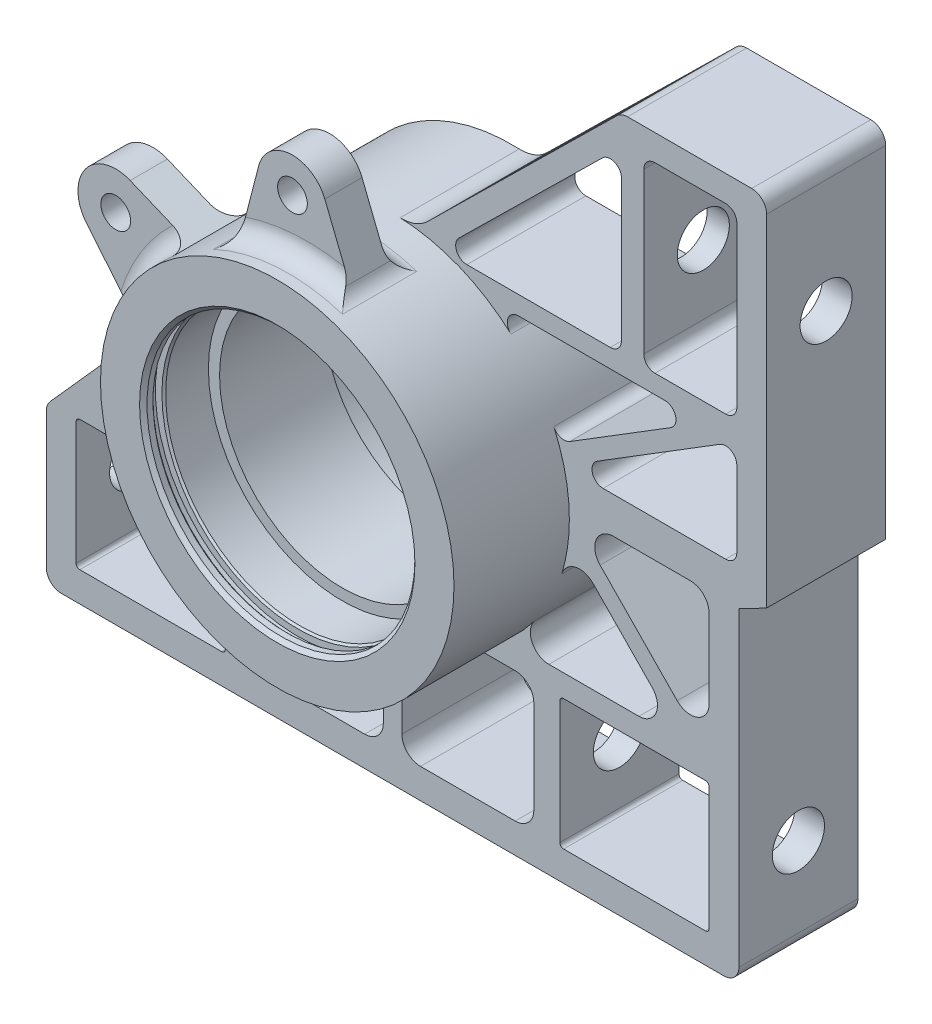
SolidWorks part; units mm, degrees
material "7075-T6 (SN)"
ref_plane "Front Plane" through (0, 0, 0) normal (0, 0, 1) x (1, 0, 0)
ref_plane "Top Plane" through (0, 0, 0) normal (0, 1, 0) x (1, 0, 0)
ref_plane "Right Plane" through (0, 0, 0) normal (1, 0, 0) x (0, 0, -1)
sketch "Sketch1" plane through (0, 0, 0) normal (0, 0, 1) x (1, 0, 0)
  circle A0 centre (0, 0) radius 36
  circle A1 centre (0, 0) radius 47.5
  dimension "D1" = 72
  dimension "D2" = 95
extrude "Boss-Extrude1" add sketch "Sketch1" along normal blind 60 and the other way blind 3
sketch "Sketch2" plane through (0, 0, -3) normal (0, 0, -1) x (-1, 0, 0)
  line L0 (0, 0) -> (0, -85.5) construction
  line L1 (-89.05, -85.5) -> (89.05, -85.5)
  line L2 (93.05, -81.5) -> (93.05, -45.0252)
  line L4 (-63.1377, 101.5) -> (-96.5, 101.5)
  line L6 (-65, -60) -> (65, -60) construction
  line L7 (-65, -60) -> (-65, 70) construction
  line L8 (-65, 70) -> (-80, 70) construction
  line L9 (-84.05, -77.5) -> (-45.95, -77.5)
  line L10 (-85.05, -76.5) -> (-85.05, -43.5)
  line L11 (-84.05, -42.5) -> (-45.95, -42.5)
  line L12 (-44.95, -76.5) -> (-44.95, -43.5)
  line L13 (-85.05, -77.5) -> (-44.95, -42.5) construction
  line L14 (-85.05, -42.5) -> (-44.95, -77.5) construction
  line L15 (45.95, -77.5) -> (84.05, -77.5)
  line L16 (44.95, -76.5) -> (44.95, -43.5)
  line L17 (45.95, -42.5) -> (84.05, -42.5)
  line L18 (85.05, -76.5) -> (85.05, -43.5)
  line L19 (44.95, -77.5) -> (85.05, -42.5) construction
  line L20 (44.95, -42.5) -> (85.05, -77.5) construction
  line L25 (-100.5, 97.5) -> (-100.5, 5.8481)
  line L26 (-89.5, 94.5) -> (-70.5, 94.5)
  line L27 (-92.5, 91.5) -> (-92.5, 48.5)
  line L28 (-89.5, 45.5) -> (-70.5, 45.5)
  line L29 (-67.5, 91.5) -> (-67.5, 48.5)
  line L30 (-92.5, 94.5) -> (-67.5, 45.5) construction
  line L31 (-92.5, 45.5) -> (-67.5, 94.5) construction
  line L32 (-93.05, -81.5) -> (-93.05, 1.9641)
  line L33 (-93.05, 1.9641) -> (-100.5, 5.8481)
  line L34 (92.0346, -42.362) -> (46.7544, 8.3829)
  line L35 (-60.3325, 100.3515) -> (-6.1946, 47.0943)
  line L36 (-61.5, 86.425) -> (-61.5, 48.5)
  line L37 (-58.5, 45.5) -> (-19.9478, 45.5)
  line L38 (-17.844, 50.6386) -> (-56.3961, 88.5636)
  line L39 (-92.5, 35.114) -> (-92.5, 14.7271)
  line L40 (-89.5, 11.7271) -> (-56.5736, 11.7271)
  line L41 (-54.9943, 17.2778) -> (-87.9207, 37.6647)
  line L42 (-74.7284, 34.9493) -> (-47.6317, 18.172)
  line L43 (-73.1491, 40.5) -> (-33.8231, 40.5)
  line L44 (-85.05, -3.0359) -> (-85.05, -24.2301)
  line L45 (-76.4741, -27.7248) -> (-55.7612, -6.5306)
  line L46 (-59.3371, 1.9641) -> (-80.05, 1.9641)
  line L47 (-69.757, -28.0053) -> (-53.8273, -11.7055)
  line L60 (-66.1811, -36.5) -> (-42, -36.5)
  line L68 (53.6007, -6.837) -> (75.599, -31.4902)
  line L69 (72.6144, -38.1534) -> (49.95, -38.1534)
  line L71 (44.95, -33.1534) -> (44.95, -15.3541)
  line L72 (-32.95, -77.5) -> (-7.5, -77.5)
  line L73 (-2.5, -72.5) -> (-2.5, -47.4342)
  line L74 (-37.95, -72.5) -> (-37.95, -47.5)
  line L75 (-32.95, -42.5) -> (-21.2132, -42.5)
  line L76 (2.5, -72.5) -> (2.5, -47.4342)
  line L77 (7.5, -77.5) -> (32.9501, -77.5)
  line L78 (37.95, -72.5331) -> (37.95, -28.5665)
  circle A0 centre (0, 0) radius 47.5 construction
  arc A1 (24.8193, 40.5) -> (-44.6143, 16.3038) centre (0, 0) ccw construction
  arc A2 (-31.8138, 35.2723) -> (-43.3166, 19.4916) centre (0, 0) ccw
  arc A3 (-46.0296, 11.7271) -> (-47.4974, 0.497) centre (0, 0) ccw construction
  arc A4 (-45.4656, -13.7526) -> (-38, -28.5) centre (0, 0) ccw
  arc A5 (-47.2398, -4.965) -> (-30.3974, -36.5) centre (0, 0) ccw construction
  circle A7 centre (0, 0) radius 47.5
  arc A9 (7.4649, -46.9098) -> (37.95, -28.5665) centre (0, 0) ccw construction
  arc A10 (44.3531, -17.0017) -> (46.9996, -6.8768) centre (0, 0) ccw
  arc A11 (43.2647, -19.6065) -> (46.6848, -8.7623) centre (0, 0) ccw construction
  arc A12 (-33.8144, -33.3592) -> (-11.3105, -46.1337) centre (0, 0) ccw
  arc A13 (-37.95, -28.5665) -> (-7.4649, -46.9098) centre (0, 0) ccw construction
  arc A16 (-45.95, -77.5) -> (-44.95, -76.5) centre (-45.95, -76.5) ccw
  arc A17 (-84.05, -77.5) -> (-85.05, -76.5) centre (-84.05, -76.5) cw
  arc A18 (-85.05, -43.5) -> (-84.05, -42.5) centre (-84.05, -43.5) cw
  arc A19 (-45.95, -42.5) -> (-44.95, -43.5) centre (-45.95, -43.5) cw
  arc A20 (45.95, -77.5) -> (44.95, -76.5) centre (45.95, -76.5) cw
  arc A21 (84.05, -77.5) -> (85.05, -76.5) centre (84.05, -76.5) ccw
  arc A22 (84.05, -42.5) -> (85.05, -43.5) centre (84.05, -43.5) cw
  arc A23 (44.95, -43.5) -> (45.95, -42.5) centre (45.95, -43.5) cw
  arc A24 (-70.5, 45.5) -> (-67.5, 48.5) centre (-70.5, 48.5) ccw
  arc A25 (-92.5, 48.5) -> (-89.5, 45.5) centre (-89.5, 48.5) ccw
  arc A26 (-89.5, 94.5) -> (-92.5, 91.5) centre (-89.5, 91.5) ccw
  arc A27 (-70.5, 94.5) -> (-67.5, 91.5) centre (-70.5, 91.5) cw
  arc A28 (-19.9478, 45.5) -> (-17.844, 50.6386) centre (-19.9478, 48.5) ccw
  arc A29 (-61.5, 48.5) -> (-58.5, 45.5) centre (-58.5, 48.5) ccw
  arc A30 (-61.5, 86.425) -> (-56.3961, 88.5636) centre (-58.5, 86.425) cw
  arc A31 (-47.6317, 18.172) -> (-43.3166, 19.4916) centre (-46.0524, 20.7226) ccw
  arc A32 (-74.7284, 34.9493) -> (-73.1491, 40.5) centre (-73.1491, 37.5) cw
  arc A33 (-33.8231, 40.5) -> (-31.8138, 35.2723) centre (-33.8231, 37.5) cw
  arc A34 (-92.5, 14.7271) -> (-89.5, 11.7271) centre (-89.5, 14.7271) ccw
  arc A35 (-56.5736, 11.7271) -> (-54.9943, 17.2778) centre (-56.5736, 14.7271) ccw
  arc A36 (-92.5, 35.114) -> (-87.9207, 37.6647) centre (-89.5, 35.114) cw
  arc A37 (-42, -36.5) -> (-38, -28.5) centre (-42, -31.5) ccw
  arc A38 (-53.8273, -11.7055) -> (-45.4656, -13.7526) centre (-50.2514, -15.2002) cw
  arc A39 (-69.757, -28.0053) -> (-66.1811, -36.5) centre (-66.1811, -31.5) ccw
  arc A40 (-85.05, -24.2301) -> (-76.4741, -27.7248) centre (-80.05, -24.2301) ccw
  arc A41 (-55.7612, -6.5306) -> (-59.3371, 1.9641) centre (-59.3371, -3.0359) ccw
  arc A42 (-85.05, -3.0359) -> (-80.05, 1.9641) centre (-80.05, -3.0359) cw
  arc A61 (89.05, -85.5) -> (93.05, -81.5) centre (89.05, -81.5) ccw
  arc A62 (-89.05, -85.5) -> (-93.05, -81.5) centre (-89.05, -81.5) cw
  arc A64 (93.05, -45.0252) -> (92.0346, -42.362) centre (89.05, -45.0252) ccw
  arc A65 (-60.3325, 100.3515) -> (-63.1377, 101.5) centre (-63.1377, 97.5) ccw
  arc A66 (-96.5, 101.5) -> (-100.5, 97.5) centre (-96.5, 97.5) ccw
  arc A67 (49.95, -38.1534) -> (44.95, -33.1534) centre (49.95, -33.1534) cw
  arc A69 (32.9501, -77.5) -> (37.95, -72.5331) centre (32.9501, -72.5) ccw
  arc A70 (2.5, -72.5) -> (7.5, -77.5) centre (7.5, -72.5) ccw
  arc A71 (-7.5, -77.5) -> (-2.5, -72.5) centre (-7.5, -72.5) ccw
  arc A72 (-32.95, -77.5) -> (-37.95, -72.5) centre (-32.95, -72.5) cw
  arc A73 (-37.95, -47.5) -> (-32.95, -42.5) centre (-32.95, -47.5) cw
  arc A74 (53.6007, -6.837) -> (46.6848, -8.7623) centre (50.6162, -9.5002) ccw
  arc A75 (75.599, -31.4902) -> (72.6144, -38.1534) centre (72.6144, -34.1534) cw
  point P6 (0, -85.5)
  point P125 (-92.5, 40.5)
  point P136 (-85.05, -36.5)
  point P139 (-47.4594, 1.9641)
  point P150 (2.5, -77.5)
  point P154 (-2.5, -77.5)
  point P163 (47.5, 0)
  point P164 (85.05, -44.3653)
  point P165 (33.4574, -33.7173)
  point P197 (93.05, -85.5)
  point P203 (93.05, -43.5)
  point P206 (-61.5, 101.5)
  point P209 (-100.5, 101.5)
  circle M4 centre (0, 0) radius 47.5
  dimension "D16" = 95
  dimension "D18" = 5
  dimension "D25" = 1
  dimension "D26" = 1
  dimension "D27" = 3
  dimension "D28" = 3
  dimension "D29" = 3
  dimension "D30" = 3
  dimension "D31" = 5
  dimension "D35" = 4
  dimension "D36" = 4
  dimension "D7" = 7
  dimension "D5" = 7
  dimension "D20" = 47.5
  dimension "D21" = 5
  dimension "D22" = 4
  dimension "D1" = 130
  dimension "D3" = 130
  dimension "D4" = 33
  dimension "D6" = 40.1
  dimension "D8" = 35
  dimension "D9" = 7
  dimension "D10" = 15
  dimension "D11" = 25
  dimension "D12" = 49
  dimension "D13" = 8
  dimension "8" = 8
  dimension "D14" = 8
  dimension "D15" = 39
  dimension "D17" = 73.5289
  dimension "D19" = 6
  dimension "D23" = 42
  dimension "D24" = 0
  dimension "D37" = 5
  dimension "D38" = 5
extrude "Boss-Extrude2" add sketch "Sketch2" against normal blind 32 contours L4 A66 L25 L33 L32 A62 L1 A61 L2 A64 L34 L35 A65 A10 L44 A42 L46 A41 L45 A40 L39 A36 L41 A35 M4 region at (89.9754, -82.4254, -3)
sketch3d "3DSketch1" plane through (0, 0, 0) normal (0, 0, 1) x (1, 0, 0)
  dimension "D1" = 10
sketch "Sketch3" plane through (0, 0, 50) normal (0, 0, 1) x (1, 0, 0)
  line L0 (-4.7305, 61.146) -> (-51.4002, 33.455) construction
  line L1 (-28.0653, 47.3005) -> (0, 0) construction
  line L2 (4.6933, 64.9164) -> (12.5436, 45.2952)
  line L3 (-4.7305, 61.146) -> (0, 0) construction
  line L4 (-14.622, 63.4221) -> (-19.361, 42.827)
  line L5 (-28.3103, 37.517) -> (-48.6575, 43.2274)
  line L6 (-51.4002, 33.455) -> (0, 0) construction
  line L7 (-45.7664, 10.6975) -> (-59.2255, 26.9908)
  circle A0 centre (0, 0) radius 61.3287 construction
  circle A1 centre (-4.7305, 61.146) radius 3.5
  circle A2 centre (-51.4002, 33.455) radius 3.5
  circle A3 centre (-4.7305, 61.146) radius 10.15
  circle A4 centre (-51.4002, 33.455) radius 10.15
  circle A5 centre (0, 0) radius 47
  point P7 (-28.0653, 47.3005)
  dimension "D1" = 55
  dimension "D2" = 20.3
  dimension "D3" = 7
  dimension "D6" = 20.3
  dimension "D8" = 16
  dimension "D9" = 94
  dimension "D4" = 54.2665
  dimension "D5" = 54.2665
  dimension "D7" = 16
fillet "Fillet4" radius 10 1 edges at (6.1946, 47.0943, 13)
sketch "Sketch4" plane through (100.5, 0, 0) normal (1, 0, 0) x (0, 0, -1)
  line L0 (-13, 94.5) -> (-13, 45.5) construction
  line L2 (-29, 94.5) -> (3, 94.5) construction
  line L3 (-29, 45.5) -> (3, 45.5) construction
  line L4 (-29, 94.5) -> (3, 94.5)
  line L5 (-29, 45.5) -> (3, 45.5)
  circle A1 centre (-13, 67) radius 7
  point P4 (-13, 70)
  dimension "D1" = 14
  dimension "D2" = 3
extrude "Cut-Extrude1" cut sketch "Sketch4" against normal up to surface (39 mm away) contours L0 A1 | A1 L0 region at (100.5, 67, 10.0291) region at (100.5, 67, 15.9709) up to face at (61.5, 67.4625, 13)
sketch "Sketch5" plane through (93.05, 0, 0) normal (1, 0, 0) x (0, 0, -1)
  line L0 (-29, -77.5) -> (3, -77.5) construction
  line L1 (-29, -42.5) -> (3, -42.5) construction
  line L2 (-29, -77.5) -> (3, -77.5)
  line L3 (-29, -42.5) -> (3, -42.5)
  line L4 (-13, -42.5) -> (-13, -77.5) construction
  circle A0 centre (-13, -60) radius 7
  dimension "D1" = 14
extrude "Cut-Extrude2" cut sketch "Sketch5" against normal blind 64 contours L4 A0 | A0 L4 region at (93.05, -60, 10.0291) region at (93.05, -60, 15.9709)
mirror "Mirror1" about plane through (0, 0, 0) normal (1, 0, 0) of "Cut-Extrude2"
ref_plane "Plane1" through (0, 0, 28.5) normal (0, 0, -1) x (-1, 0, 0)
sketch "Sketch6" plane through (0, 0, 28.5) normal (0, 0, -1) x (-1, 0, 0)
  circle A0 centre (0, 0) radius 36
  circle A1 centre (0, 0) radius 33
  dimension "D1" = 66
extrude "Boss-Extrude4" add sketch "Sketch6" along normal blind 14 and the other way blind 14
fillet "Fillet5" radius 4 3 edges at (2.5, -47.4342, 13) (-2.5, -47.4342, 13) (-37.95, -28.5665, 13)
ref_plane "Plane2" through (0, 0, 52) normal (0, 0, 1) x (1, 0, 0)
sketch "Sketch8" plane through (0, 0, 52) normal (0, 0, 1) x (1, 0, 0)
  line L0 (-3.9095, 61.2013) -> (-51.3974, 33.4542) construction
  line L1 (-27.6534, 47.3277) -> (0, 0) construction
  line L2 (4.7875, 64.6809) -> (12.5436, 45.2952)
  line L3 (-3.9095, 61.2013) -> (0, 0) construction
  line L4 (-12.9785, 63.546) -> (-18.205, 43.331)
  line L6 (-51.3974, 33.4542) -> (0, 0) construction
  line L7 (-45.7661, 10.6988) -> (-59.223, 26.9902)
  line L8 (-30.4779, 35.7784) -> (-48.0729, 43.0634)
  line L9 (-48.0729, 43.0634) -> (-48.6548, 43.2267)
  circle A0 centre (0, 0) radius 61.326 construction
  circle A1 centre (-3.9095, 61.2013) radius 4
  circle A2 centre (-51.3974, 33.4542) radius 4
  circle A3 centre (-3.9095, 61.2013) radius 9.3672
  circle A4 centre (-51.3974, 33.4542) radius 10.15
  circle A5 centre (0, 0) radius 47
  point P6 (-27.6534, 47.3277)
  dimension "D2" = 8
  dimension "D3" = 8
  dimension "D1" = 55
extrude "Boss-Extrude6" add sketch "Sketch8" against normal blind 10 contours A5 A4 L7 | A4 A2 | A5 L2 A3 L4 | A3 A1 region at (-3.242, 50.7524, 52) region at (5.0285, 62.9229, 52) region at (-43.203, 26.4175, 52) region at (-59.6635, 38.8346, 52)
fillet "Fillet12" radius 5 7 edges at (-3.0281, 47.4034, 42) (12.3109, 45.8769, 47) (-3.0281, 47.4034, 52) (-18.0482, 43.9376, 47) (-40.526, 24.7768, 42) (-40.526, 24.7768, 52) (-46.1651, 11.1819, 47)
ref_plane "Plane3" through (0, 0, 86.5) normal (0, 0, 1) x (1, 0, 0)
mirror "Mirror2" about plane through (0, 0, 86.5) normal (0, 0, 1) of bodies 112
delete or keep bodies "Body-Delete/Keep 1" type delete bodies bodies 113
ref_plane "Plane4" through (0, 0, 0) normal (0, 0, -1) x (-1, 0, 0)
sketch "Sketch9" plane through (0, 0, 0) normal (0, 0, -1) x (-1, 0, 0)
  circle A0 centre (0, 0) radius 36
  circle A1 centre (0, 0) radius 38.25
  dimension "D1" = 76.5
extrude "Cut-Extrude3" cut sketch "Sketch9" against normal blind 2.4
chamfer "Chamfer1" distance 0.5 angle 45 1 edges at (-36, 0, 0)
chamfer "Chamfer2" distance 1 angle 45 1 edges at (36, 0, -3)
chamfer "Chamfer3" distance 0.5 angle 45 1 edges at (-36, 0, 2.4)
ref_plane "Plane5" through (0, 0, 56.9) normal (0, 0, 1) x (1, 0, 0)
sketch "Sketch10" plane through (0, 0, 56.9) normal (0, 0, 1) x (1, 0, 0)
  circle A0 centre (0, 0) radius 36
  circle A1 centre (0, 0) radius 38.25
extrude "Cut-Extrude4" cut sketch "Sketch10" against normal blind 2.4
chamfer "Chamfer4" distance 0.5 angle 45 2 edges at (36, 0, 56.9) (36, 0, 54.5)
chamfer "Chamfer5" distance 1 angle 45 1 edges at (36, 0, 60)
